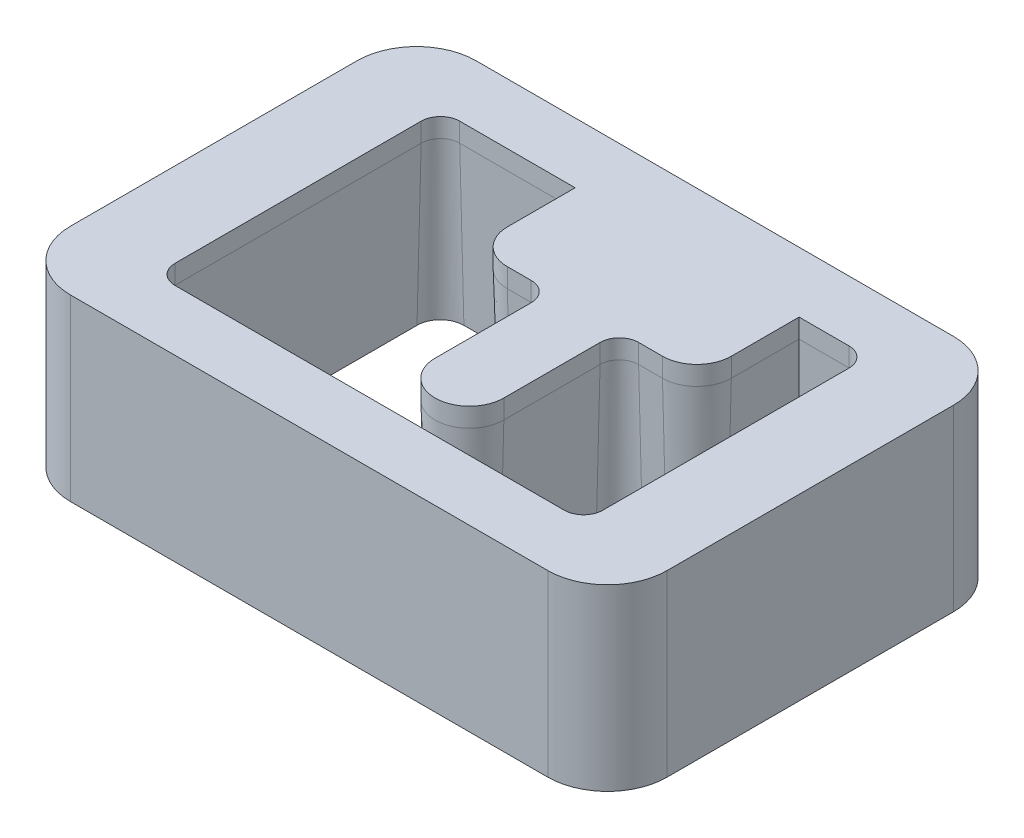
SolidWorks part; units mm, degrees
material "K110"
ref_plane "Front Plane" through (0, 0, 0) normal (0, 0, 1) x (1, 0, 0)
ref_plane "Top Plane" through (0, 0, 0) normal (0, 1, 0) x (1, 0, 0)
ref_plane "Right Plane" through (0, 0, 0) normal (1, 0, 0) x (0, 0, -1)
sketch "Sketch1" plane through (0, 0, 0) normal (0, 1, 0) x (1, 0, 0)
  line L1 (-50, -34) -> (50, -34)
  line L2 (-50, -34) -> (-50, 34)
  line L3 (-50, 34) -> (50, 34)
  line L4 (50, -34) -> (50, 34)
  line L5 (-50, -34) -> (50, 34) construction
  line L6 (-50, 34) -> (50, -34) construction
  point P0 (0, 0)
  dimension "D1" = 68
  dimension "D2" = 100
extrude "Boss-Extrude1" add sketch "Sketch1" against normal blind 30
fillet "Fillet1" radius 10 4 edges at (-50, -15, -34) (50, -15, -34) (50, -15, 34) (-50, -15, 34)
sketch "Sketch2" plane through (0, 0, 0) normal (0, 1, 0) x (1, 0, 0)
  line L22 (-32.625, -23.86) -> (32.625, -23.86)
  line L23 (-35.855, 20.63) -> (-35.855, -20.63)
  line L24 (-13.275, 23.86) -> (-32.625, 23.86)
  line L25 (-13.275, 12.5) -> (-13.275, 23.86)
  line L26 (-3.505, 6.73) -> (-7.505, 6.73)
  line L27 (-0.275, -12.63) -> (-0.275, 3.5)
  line L28 (11.265, 3.5) -> (11.265, -12.63)
  line L29 (18.495, 6.73) -> (14.495, 6.73)
  line L30 (24.265, 23.86) -> (24.265, 12.5)
  line L31 (32.625, 23.86) -> (24.265, 23.86)
  line L32 (35.855, -20.63) -> (35.855, 20.63)
  line L33 (-32.625, -23.86) -> (32.625, -23.86)
  line L34 (-35.855, 20.63) -> (-35.855, -20.63)
  line L35 (-13.275, 23.86) -> (-32.625, 23.86)
  line L36 (-13.275, 12.5) -> (-13.275, 23.86)
  line L37 (-3.505, 6.73) -> (-7.505, 6.73)
  line L38 (-0.275, -12.63) -> (-0.275, 3.5)
  line L39 (11.265, 3.5) -> (11.265, -12.63)
  line L40 (18.495, 6.73) -> (14.495, 6.73)
  line L41 (24.265, 23.86) -> (24.265, 12.5)
  line L42 (32.625, 23.86) -> (24.265, 23.86)
  line L43 (35.855, -20.63) -> (35.855, 20.63)
  arc A18 (32.625, -23.86) -> (35.855, -20.63) centre (32.625, -20.63) ccw
  arc A19 (-35.855, -20.63) -> (-32.625, -23.86) centre (-32.625, -20.63) ccw
  arc A20 (-32.625, 23.86) -> (-35.855, 20.63) centre (-32.625, 20.63) ccw
  arc A21 (-13.275, 12.5) -> (-7.505, 6.73) centre (-7.505, 12.5) ccw
  arc A22 (-0.275, 3.5) -> (-3.505, 6.73) centre (-3.505, 3.5) ccw
  arc A23 (-0.275, -12.63) -> (11.265, -12.63) centre (5.495, -12.63) ccw
  arc A24 (14.495, 6.73) -> (11.265, 3.5) centre (14.495, 3.5) ccw
  arc A25 (18.495, 6.73) -> (24.265, 12.5) centre (18.495, 12.5) ccw
  arc A26 (35.855, 20.63) -> (32.625, 23.86) centre (32.625, 20.63) ccw
  arc A27 (32.625, -23.86) -> (35.855, -20.63) centre (32.625, -20.63) ccw
  arc A28 (-35.855, -20.63) -> (-32.625, -23.86) centre (-32.625, -20.63) ccw
  arc A29 (-32.625, 23.86) -> (-35.855, 20.63) centre (-32.625, 20.63) ccw
  arc A30 (-13.275, 12.5) -> (-7.505, 6.73) centre (-7.505, 12.5) ccw
  arc A31 (-0.275, 3.5) -> (-3.505, 6.73) centre (-3.505, 3.5) ccw
  arc A32 (-0.275, -12.63) -> (11.265, -12.63) centre (5.495, -12.63) ccw
  arc A33 (14.495, 6.73) -> (11.265, 3.5) centre (14.495, 3.5) ccw
  arc A34 (18.495, 6.73) -> (24.265, 12.5) centre (18.495, 12.5) ccw
  arc A35 (35.855, 20.63) -> (32.625, 23.86) centre (32.625, 20.63) ccw
  dimension "D1" = 0.23
extrude "Cut-Extrude1" cut sketch "Sketch2" against normal up to next
sketch "Sketch3" plane through (0, 0, 0) normal (0, 0, 1) x (1, 0, 0)
  line L6 (35.855, -3.2) -> (36.5568, -30)
  line L7 (40, -30) -> (40, 0) construction
  line L8 (40, -30) -> (50, -30) construction
  line L11 (37.4, 0) -> (-37.4, 0) construction
  line L12 (36.5568, -30) -> (34.855, -30)
  line L13 (-40, -30) -> (40, -30) construction
  line L14 (34.855, -3.2) -> (35.855, -3.2)
  line L15 (34.855, -30) -> (34.855, -3.2)
  line L16 (35.855, -30) -> (35.855, 0) construction
  dimension "D1" = 3.2
  dimension "D2" = 1.5
  dimension "D3" = 1
sketch "Sketch5" plane through (0, 0, 0) normal (0, 1, 0) x (1, 0, 0)
  line L0 (32.625, 23.86) -> (24.265, 23.86) construction
  line L1 (35.855, -20.63) -> (35.855, 20.63) construction
  line L2 (24.265, 23.86) -> (24.265, 12.5) construction
  line L3 (18.495, 6.73) -> (14.495, 6.73) construction
  line L4 (11.265, 3.5) -> (11.265, -12.63) construction
  line L5 (-0.275, -12.63) -> (-0.275, 3.5) construction
  line L6 (-3.505, 6.73) -> (-7.505, 6.73) construction
  line L7 (-13.275, 12.5) -> (-13.275, 23.86) construction
  line L8 (-13.275, 23.86) -> (-32.625, 23.86) construction
  line L9 (-35.855, 20.63) -> (-35.855, -20.63) construction
  line L10 (-32.625, -23.86) -> (32.625, -23.86) construction
  line L11 (-32.625, -23.86) -> (32.625, -23.86)
  line L12 (-35.855, 20.63) -> (-35.855, -20.63)
  line L13 (-13.275, 23.86) -> (-32.625, 23.86)
  line L14 (-13.275, 12.5) -> (-13.275, 23.86)
  line L15 (-3.505, 6.73) -> (-7.505, 6.73)
  line L16 (-0.275, -12.63) -> (-0.275, 3.5)
  line L17 (11.265, 3.5) -> (11.265, -12.63)
  line L18 (18.495, 6.73) -> (14.495, 6.73)
  line L19 (24.265, 23.86) -> (24.265, 12.5)
  line L20 (35.855, -20.63) -> (35.855, 20.63)
  line L21 (32.625, 23.86) -> (24.265, 23.86)
  arc A0 (-0.275, 3.5) -> (-3.505, 6.73) centre (-3.505, 3.5) ccw construction
  arc A1 (35.855, 20.63) -> (32.625, 23.86) centre (32.625, 20.63) ccw construction
  arc A2 (18.495, 6.73) -> (24.265, 12.5) centre (18.495, 12.5) ccw construction
  arc A3 (14.495, 6.73) -> (11.265, 3.5) centre (14.495, 3.5) ccw construction
  arc A4 (-0.275, -12.63) -> (11.265, -12.63) centre (5.495, -12.63) ccw construction
  arc A5 (-13.275, 12.5) -> (-7.505, 6.73) centre (-7.505, 12.5) ccw construction
  arc A6 (-32.625, 23.86) -> (-35.855, 20.63) centre (-32.625, 20.63) ccw construction
  arc A7 (-35.855, -20.63) -> (-32.625, -23.86) centre (-32.625, -20.63) ccw construction
  arc A8 (32.625, -23.86) -> (35.855, -20.63) centre (32.625, -20.63) ccw construction
  arc A9 (32.625, -23.86) -> (35.855, -20.63) centre (32.625, -20.63) ccw
  arc A10 (-35.855, -20.63) -> (-32.625, -23.86) centre (-32.625, -20.63) ccw
  arc A11 (-32.625, 23.86) -> (-35.855, 20.63) centre (-32.625, 20.63) ccw
  arc A12 (-13.275, 12.5) -> (-7.505, 6.73) centre (-7.505, 12.5) ccw
  arc A13 (-0.275, 3.5) -> (-3.505, 6.73) centre (-3.505, 3.5) ccw
  arc A14 (-0.275, -12.63) -> (11.265, -12.63) centre (5.495, -12.63) ccw
  arc A15 (14.495, 6.73) -> (11.265, 3.5) centre (14.495, 3.5) ccw
  arc A16 (18.495, 6.73) -> (24.265, 12.5) centre (18.495, 12.5) ccw
  arc A17 (35.855, 20.63) -> (32.625, 23.86) centre (32.625, 20.63) ccw
sweep "Cut-Sweep1" cut profiles "Sketch3" path "Sketch5"
hole_wizard "M6 Tapped Hole1" positions "Sketch11" profile "Sketch9" tap size "M6" standard "ISO"
sketch "Sketch11" plane through (0, -30, 0) normal (0, -1, 0) x (-1, 0, 0)
  line L0 (-40, 34) -> (40, 34) construction
  line L1 (-50, -24) -> (-50, 24) construction
  line L2 (50, 24) -> (50, -24) construction
  line L3 (40, -34) -> (-40, -34) construction
  point P0 (-43, 27)
  point P2 (43, 27)
  point P4 (43, -27)
  point P6 (-43, -27)
  dimension "D1" = 7
  dimension "D2" = 7
  dimension "D3" = 7
  dimension "D4" = 7
sketch "Sketch9" plane through (43, -30, -27) normal (1, 0, 0) x (0, 0, -1)
  line L0 (0, 0) -> (0, 18.5022)
  line L1 (0, 18.5022) -> (2.5, 17)
  line L2 (2.5, 17) -> (2.5, 0.525)
  line L3 (2.5, 0.525) -> (3.025, 0)
  line L5 (3.025, 0) -> (0, 0)
  line L6 (-2.5, 0.525) -> (-3.025, 0) construction
  line L10 (0, 18.5022) -> (-2.5, 17) construction
  line L11 (0, -6.35) -> (0, 107.95) construction
  dimension "Tap Drill Dia." = 5
  dimension "Tap Drill Depth" = 17
  dimension "Near C'Sink Dia." = 6.05
  dimension "Near C'Sink Angle" = 90
  dimension "Drill Angle" = 118
cosmetic thread "Hole Thread1"
cosmetic thread "Hole Thread2"
cosmetic thread "Hole Thread3"
cosmetic thread "Hole Thread4"
